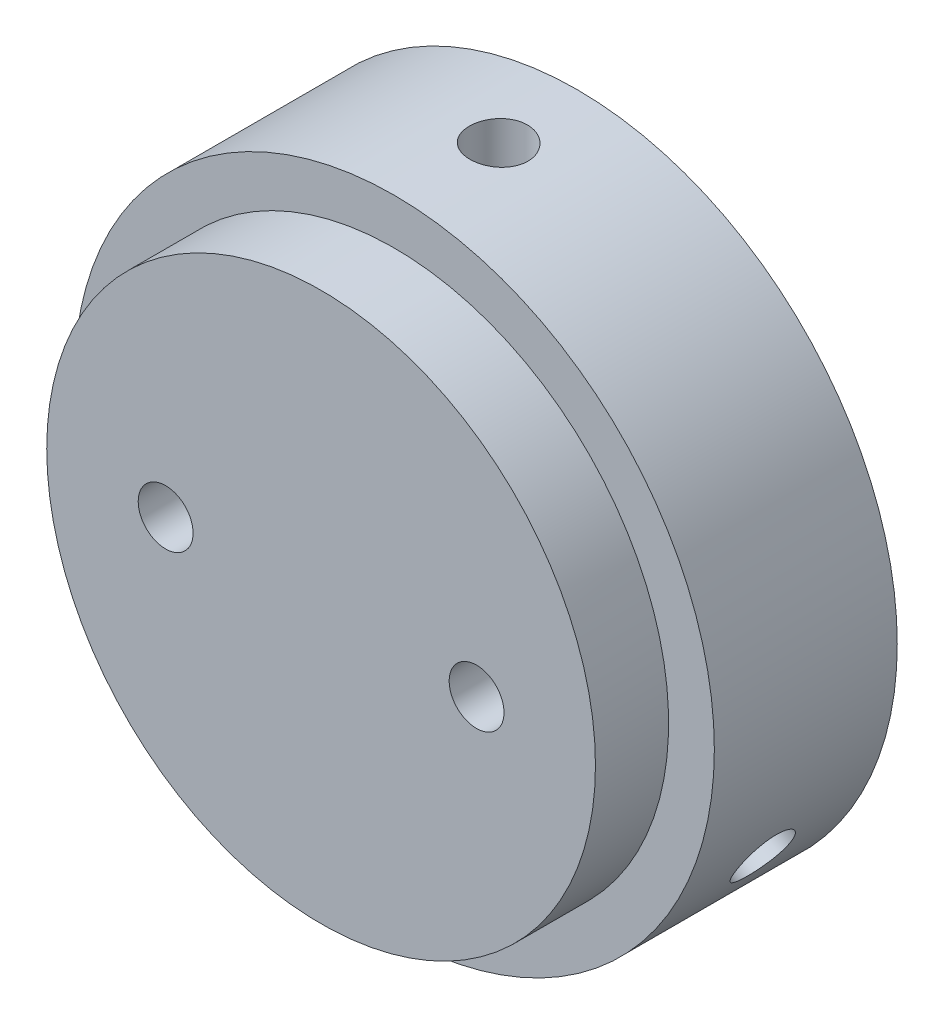
SolidWorks part; units mm, degrees
ref_plane "Front Plane" through (0, 0, 0) normal (0, 0, 1) x (1, 0, 0)
ref_plane "Top Plane" through (0, 0, 0) normal (0, 1, 0) x (1, 0, 0)
ref_plane "Right Plane" through (0, 0, 0) normal (1, 0, 0) x (0, 0, -1)
sketch "Sketch1" plane through (0, 0, 0) normal (0, 0, 1) x (1, 0, 0)
  circle A0 centre (0, 0) radius 15
  circle A1 centre (-8.5, 0) radius 1.5
  circle A2 centre (8.5, 0) radius 1.5
  point P3 (0, 0)
  dimension "D1" = 30
  dimension "D4" = 3
  dimension "D5" = 3
  dimension "D3" = 8.5
  dimension "D2" = 8.5
extrude "Boss-Extrude1" add sketch "Sketch1" along normal blind 4
sketch "Sketch2" plane through (0, 0, 0) normal (0, 0, -1) x (-1, 0, 0)
  line L0 (0, 0) -> (0, 18.35) construction
  point P17 (0, 0)
  dimension "D1" = 18.35
sketch "Sketch4" plane through (0, 0, 0) normal (0, 0, -1) x (-1, 0, 0)
  line L0 (0, 0) -> (0, 0.5) construction
  circle A1 centre (0, 0.5) radius 2.5
  circle A2 centre (0, 0) radius 17.5
  circle A3 centre (8.5, 0) radius 1.5
  circle A4 centre (-8.5, 0) radius 1.5
  dimension "D1" = 5
  dimension "D3" = 35
  dimension "D2" = 0.5
extrude "Boss-Extrude2" add sketch "Sketch4" along normal blind 10
ref_plane "Plane1" through (0, 12.5, 0) normal (0, 1, 0) x (1, 0, 0)
sketch "Sketch5" plane through (0, 12.5, 0) normal (0, 1, 0) x (1, 0, 0)
  circle A0 centre (5, 0) radius 1.6
  dimension "D1" = 3.2
  dimension "D2" = 5
  dimension "D3" = 12.5
ref_plane "Plane2" through (0, 1.5, 0) normal (0, 1, 0) x (1, 0, 0)
sketch "Sketch9" plane through (0, 0, 4) normal (0, 0, 1) x (1, 0, 0)
  circle A0 centre (0, 0) radius 8.75
  dimension "D1" = 17.5
sketch "Sketch12" plane through (0, 0, -10) normal (0, 0, -1) x (-1, 0, 0)
  line L2 (1.0981, -4.0981) -> (4.0981, 1.0981)
  line L3 (4.0981, 1.0981) -> (6.4796, -0.2769)
  line L4 (6.4796, -0.2769) -> (3.4796, -5.4731)
  line L5 (3.4796, -5.4731) -> (1.0981, -4.0981)
  line L6 (-2.75, 4.5) -> (2.75, 4.5)
  line L7 (-2.75, 4.5) -> (-2.75, 2)
  line L8 (-2.75, 2) -> (2.75, 2)
  line L9 (2.75, 4.5) -> (2.75, 2)
  line L10 (0, 0.5) -> (0, -6.5) construction
  line L11 (-3.4796, -5.4731) -> (-1.0981, -4.0981)
  line L12 (-6.4796, -0.2769) -> (-3.4796, -5.4731)
  line L13 (-4.0981, 1.0981) -> (-6.4796, -0.2769)
  line L14 (-1.0981, -4.0981) -> (-4.0981, 1.0981)
  circle A0 centre (0, 0) radius 17.5 construction
  point P1 (0, 2)
  point P2 (2.5981, -1.5)
  dimension "D1" = 5.5
  dimension "D2" = 2
  dimension "D3" = 3
  dimension "D4" = 2.5
  dimension "D5" = 6
  dimension "D6" = 2.75
extrude "Cut-Extrude7" cut sketch "Sketch12" against normal blind 10
ref_plane "Plane3" through (-6.4796, -0.2769, -10) normal (-0.5, 0.866, 0) x (0.866, 0.5, 0)
sketch "Sketch16" plane through (0, 0, -10) normal (0, 0, -1) x (-1, 0, 0)
  line L0 (-2.5981, -1.5) -> (-15.1554, -8.75)
  line L1 (-1.0981, -4.0981) -> (-4.0981, 1.0981) construction
  line L2 (-2.5981, -1.5) -> (-1.9158, -1.1061)
  circle A0 centre (0, 0) radius 17.5 construction
  arc A1 (-2, 2) -> (2, 2) centre (0, 0.5) ccw construction
sketch "Sketch17" plane through (2.5981, -1.5, 0) normal (0.866, -0.5, 0) x (0, 0, -1)
  line L0 (10, 0) -> (5, 0)
  line L1 (10, -3) -> (10, 3) construction
  circle A0 centre (5, 0) radius 1.6
  dimension "D3" = 3.2
  dimension "D1" = 5
  dimension "D2" = 0
  dimension "D4" = 0
extrude "Cut-Extrude8" cut sketch "Sketch17" along normal blind 15 and the other way blind 2 contours A0 region at (2.5981, -1.5, -3.4453)
sketch "Sketch18" plane through (-2.5981, -1.5, 0) normal (-0.866, -0.5, 0) x (0, 0, 1)
  line L0 (-10, 0) -> (-5, 0)
  line L1 (-10, 3) -> (-10, -3) construction
  circle A0 centre (-5, 0) radius 1.6
  dimension "D3" = 3.2
  dimension "D1" = 5
  dimension "D2" = 0
extrude "Cut-Extrude9" cut sketch "Sketch18" against normal blind 2 and the other way blind 30 contours A0 region at (-1.8207, -2.8464, -5)
sketch "Sketch20" plane through (-4.9796, -2.875, 0) normal (0.866, 0.5, 0) x (0, 0, -1)
  circle A0 centre (5, 0) radius 3.1
  dimension "D1" = 6.2
sketch "Sketch21" plane through (4.9796, -2.875, 0) normal (-0.866, 0.5, 0) x (0, 0, 1)
  circle A0 centre (-5, 0) radius 3.1
  dimension "D1" = 6.2
sketch "Esboço1" plane through (0, 4.5, 0) normal (0, -1, 0) x (-1, 0, 0)
  line L0 (0, 0) -> (0, 9.6637)
sketch "Esboço2" plane through (0, 4.5, 0) normal (0, -1, 0) x (1, 0, 0)
  circle A0 centre (0.3378, -5.3695) radius 1.6
  dimension "D1" = 3.2
extrude "Corte-extrusão1" cut sketch "Esboço2" against normal blind 15
equation "\"mm\"=1.5"
